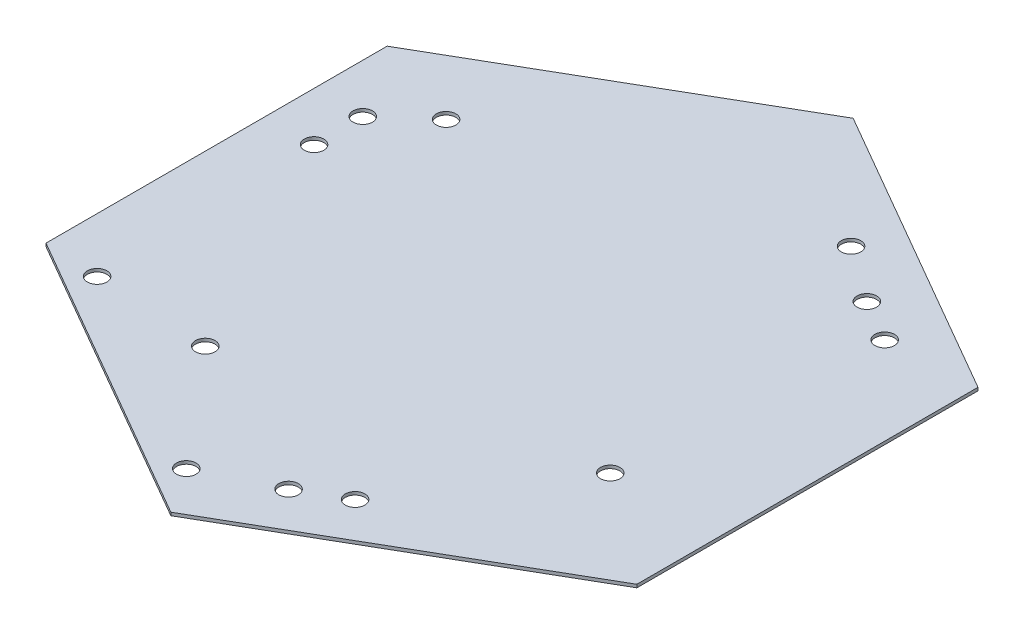
SolidWorks part; units mm, degrees
material "5052-H32"
ref_plane "Front Plane" through (0, 0, 0) normal (0, 0, 1) x (1, 0, 0)
ref_plane "Top Plane" through (0, 0, 0) normal (0, 1, 0) x (1, 0, 0)
ref_plane "Right Plane" through (0, 0, 0) normal (1, 0, 0) x (0, 0, -1)
sketch "Sketch1" plane through (0, 0, 0) normal (0, 1, 0) x (1, 0, 0)
  line L0 (10.1478, -68.3765) -> (21.1463, -62.0265) construction
  line L1 (0, 88.9) -> (-76.9897, 44.45)
  line L2 (-76.9897, 44.45) -> (-76.9897, -44.45)
  line L3 (-76.9897, -44.45) -> (0, -88.9)
  line L4 (0, -88.9) -> (76.9897, -44.45)
  line L5 (76.9897, -44.45) -> (76.9897, 44.45)
  line L6 (76.9897, 44.45) -> (0, 88.9)
  line L7 (21.1463, -62.0265) -> (27.4963, -73.025) construction
  line L8 (-64.2897, 25.4) -> (-64.2897, 12.7) construction
  line L9 (-64.2897, 12.7) -> (-76.9897, 12.7) construction
  line L10 (54.1419, 42.9765) -> (43.1434, 49.3265) construction
  line L11 (43.1434, 49.3265) -> (49.4934, 60.325) construction
  circle A0 centre (0, 0) radius 76.9897 construction
  circle A1 centre (10.1478, -68.3765) radius 2.54
  circle A2 centre (21.1463, -62.0265) radius 2.54
  circle A3 centre (-64.2897, 25.4) radius 2.54
  circle A4 centre (-64.2897, 12.7) radius 2.54
  circle A5 centre (54.1419, 42.9765) radius 2.54
  circle A6 centre (43.1434, 49.3265) radius 2.54
  point P13 (38.4948, -66.675)
  point P28 (0, 0)
  dimension "D2" = 5.08
  dimension "D3" = 12.7
  dimension "D4" = 12.7
  dimension "D1" = 177.8
  dimension "D5" = 12.7
  dimension "D6" = 3
extrude "Boss-Extrude1" add sketch "Sketch1" along normal blind 0.8128
sketch "Sketch2" plane through (0, 0.8128, 0) normal (0, 1, 0) x (1, 0, 0)
  line L1 (17.6188, -76.1634) -> (79.2138, 30.5223) construction
  line L2 (17.6188, -76.1634) -> (-83.5676, -17.7434) construction
  line L3 (-83.5676, -17.7434) -> (-21.9726, 88.9423) construction
  line L4 (79.2138, 30.5223) -> (-21.9726, 88.9423) construction
  line L7 (-76.9897, -44.45) -> (0, -88.9) construction
  circle A0 centre (28.6206, 59.7323) radius 2.54
  circle A1 centre (48.4163, -22.8205) radius 2.54
  circle A2 centre (-52.7701, 35.5995) radius 2.54
  circle A3 centre (-32.9744, -46.9534) radius 2.54
  dimension "D5" = 5.08
  dimension "D1" = 123.19
  dimension "D2" = 116.84
  dimension "D3" = 57.15
  dimension "D4" = 53.34
extrude "Cut-Extrude1" cut sketch "Sketch2" against normal through all
sketch "Sketch3" plane through (0, 0.8128, 0) normal (0, 1, 0) x (1, 0, 0)
  line L0 (-62.8161, -45.3007) -> (-65.9911, -50.8) construction
  line L2 (-76.9897, -44.45) -> (0, -88.9) construction
  line L3 (-62.8161, -45.3007) -> (-7.8235, -77.0507) construction
  line L4 (-35.3198, -61.1757) -> (-38.4948, -66.675) construction
  circle A1 centre (-7.8235, -77.0507) radius 2.54
  circle A2 centre (-62.8161, -45.3007) radius 2.54
  dimension "D1" = 5.08
  dimension "D2" = 6.35
  dimension "D3" = 63.5
extrude "Cut-Extrude2" cut sketch "Sketch3" against normal through all
